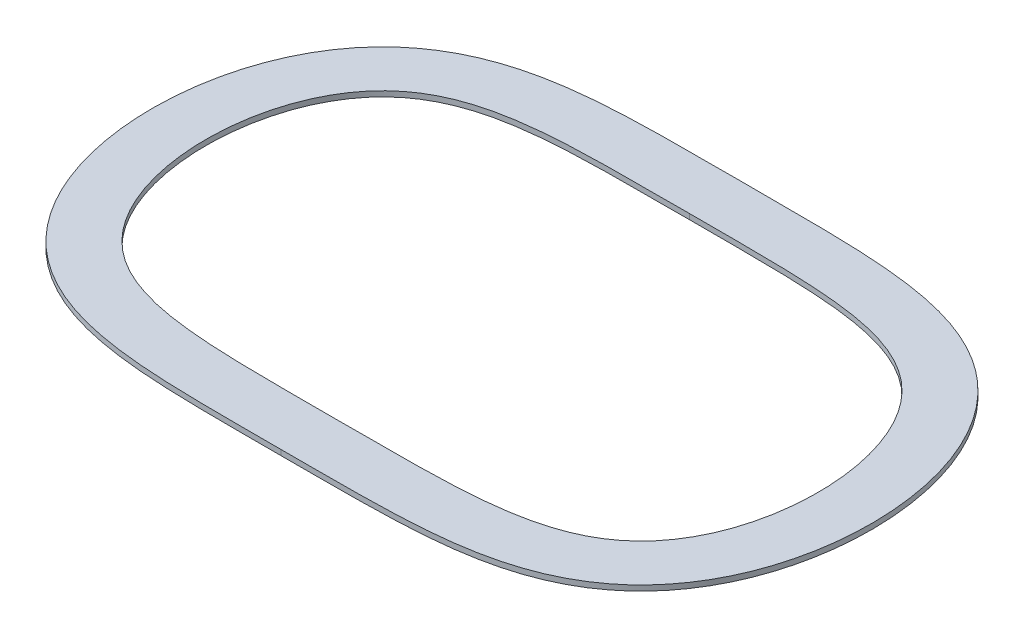
SolidWorks part; units mm, degrees
ref_plane "Front Plane" through (0, 0, 0) normal (0, 0, 1) x (1, 0, 0)
ref_plane "Top Plane" through (0, 0, 0) normal (0, 1, 0) x (1, 0, 0)
ref_plane "Right Plane" through (0, 0, 0) normal (1, 0, 0) x (0, 0, -1)
sketch "Sketch1" plane through (0, 0, 0) normal (0, 1, 0) x (1, 0, 0)
  spline S0 degree 4 poles (0, 129.0994) (4.3298, 129.0999) (12.9895, 129.0995) (25.9763, 129.0992) (43.2902, 129.014) (60.6007, 128.6712) (77.8947, 127.8129) (95.543, 126.046) (113.014, 122.896) (130.0464, 117.7971) (146.1581, 110.2269) (160.4313, 100.265) (172.6933, 87.9119) (182.6634, 73.6634) (190.3404, 58.0791) (195.8654, 41.6227) (199.4008, 24.6362) (201.0699, 7.3707) (200.9352, -9.9735) (198.9912, -27.2107) (195.1663, -44.1354) (189.3287, -60.4854) (181.3147, -75.9018) (170.9944, -89.9023) (157.8662, -102.4377) (141.9679, -112.6829) (124.642, -119.7567) (106.7084, -124.2192) (88.4462, -126.9034) (70.0513, -128.3227) (45.6298, -129.0998) (25.3491, -129.0993) (10.1399, -129.0994) (0, -129.0994) knots 0 0 0 0 0 0.03122 0.06244 0.093642 0.124843 0.156053 0.187263 0.221451 0.252662 0.283872 0.315082 0.346292 0.377502 0.408713 0.439923 0.471133 0.502344 0.533554 0.564765 0.595975 0.627185 0.658396 0.689606 0.720816 0.757371 0.793926 0.823852 0.853778 0.890332 0.926886 1 1 1 1 1 construction
  spline S1 degree 4 poles (0, 129.0994) (4.3298, 129.0999) (12.9895, 129.0995) (25.9763, 129.0992) (43.2902, 129.014) (60.6007, 128.6712) (77.8947, 127.8129) (95.543, 126.046) (113.014, 122.896) (130.0464, 117.7971) (146.1581, 110.2269) (160.4313, 100.265) (172.6933, 87.9119) (182.6634, 73.6634) (190.3404, 58.0791) (195.8654, 41.6227) (199.4008, 24.6362) (201.0699, 7.3707) (200.9352, -9.9735) (198.9912, -27.2107) (195.1663, -44.1354) (189.3287, -60.4854) (181.3147, -75.9018) (170.9944, -89.9023) (157.8662, -102.4377) (141.9679, -112.6829) (124.642, -119.7567) (106.7084, -124.2192) (88.4462, -126.9034) (70.0513, -128.3227) (45.6298, -129.0998) (25.3491, -129.0993) (10.1399, -129.0994) (0, -129.0994) knots 0 0 0 0 0 0.03122 0.06244 0.093642 0.124843 0.156053 0.187263 0.221451 0.252662 0.283872 0.315082 0.346292 0.377502 0.408713 0.439923 0.471133 0.502344 0.533554 0.564765 0.595975 0.627185 0.658396 0.689606 0.720816 0.757371 0.793926 0.823852 0.853778 0.890332 0.926886 1 1 1 1 1
  spline S2 degree 4 poles (0, 129.0994) (-4.3298, 129.0999) (-12.9895, 129.0995) (-25.9763, 129.0992) (-43.2902, 129.014) (-60.6007, 128.6712) (-77.8947, 127.8129) (-95.543, 126.046) (-113.014, 122.896) (-130.0464, 117.7971) (-146.1581, 110.2269) (-160.4313, 100.265) (-172.6933, 87.9119) (-182.6634, 73.6634) (-190.3404, 58.0791) (-195.8654, 41.6227) (-199.4008, 24.6362) (-201.07, 7.3707) (-200.9352, -9.9735) (-198.9912, -27.2107) (-195.1663, -44.1354) (-189.3287, -60.4854) (-181.3147, -75.9018) (-170.9944, -89.9023) (-157.8662, -102.4377) (-141.9679, -112.6829) (-124.642, -119.7567) (-106.7084, -124.2192) (-88.4462, -126.9034) (-70.0513, -128.3227) (-45.6298, -129.0998) (-25.3491, -129.0993) (-10.1399, -129.0994) (0, -129.0994) knots 0 0 0 0 0 0.03122 0.06244 0.093642 0.124843 0.156053 0.187263 0.221451 0.252662 0.283872 0.315082 0.346292 0.377502 0.408713 0.439923 0.471133 0.502344 0.533554 0.564765 0.595975 0.627185 0.658396 0.689606 0.720816 0.757371 0.793926 0.823852 0.853778 0.890332 0.926886 1 1 1 1 1 construction
  spline S3 degree 4 poles (0, 129.0994) (-4.3298, 129.0999) (-12.9895, 129.0995) (-25.9763, 129.0992) (-43.2902, 129.014) (-60.6007, 128.6712) (-77.8947, 127.8129) (-95.543, 126.046) (-113.014, 122.896) (-130.0464, 117.7971) (-146.1581, 110.2269) (-160.4313, 100.265) (-172.6933, 87.9119) (-182.6634, 73.6634) (-190.3404, 58.0791) (-195.8654, 41.6227) (-199.4008, 24.6362) (-201.07, 7.3707) (-200.9352, -9.9735) (-198.9912, -27.2107) (-195.1663, -44.1354) (-189.3287, -60.4854) (-181.3147, -75.9018) (-170.9944, -89.9023) (-157.8662, -102.4377) (-141.9679, -112.6829) (-124.642, -119.7567) (-106.7084, -124.2192) (-88.4462, -126.9034) (-70.0513, -128.3227) (-45.6298, -129.0998) (-25.3491, -129.0993) (-10.1399, -129.0994) (0, -129.0994) knots 0 0 0 0 0 0.03122 0.06244 0.093642 0.124843 0.156053 0.187263 0.221451 0.252662 0.283872 0.315082 0.346292 0.377502 0.408713 0.439923 0.471133 0.502344 0.533554 0.564765 0.595975 0.627185 0.658396 0.689606 0.720816 0.757371 0.793926 0.823852 0.853778 0.890332 0.926886 1 1 1 1 1
extrude "body" add sketch "Sketch1" along normal blind 3 contours S1 S3
sketch "Sketch6" plane through (0, 3, 0) normal (0, 1, 0) x (1, 0, 0)
  spline S5 degree 3 poles (-1285.0609, -2635.3961) (-864.743, -75.7384) (-425.088, -99.3062) (19.1852, -99.0955) (23.9815, -99.0904) (33.5738, -99.0537) (38.3699, -99.0221) (47.9616, -98.8962) (52.7579, -98.802) (62.3467, -98.4962) (67.1336, -98.285) (76.6828, -97.6696) (81.4451, -97.2657) (90.9316, -96.1585) (95.6558, -95.456) (102.6989, -94.0635) (105.0393, -93.5425) (108.5366, -92.6558) (109.7001, -92.3427) (112.0221, -91.6775) (113.1817, -91.3249) (118.9246, -89.468) (123.3747, -87.6745) (129.7643, -84.3748) (131.8465, -83.1733) (134.8899, -81.2003) (135.894, -80.5119) (137.8536, -79.0903) (138.8101, -78.3567) (143.4771, -74.5763) (146.8407, -71.1906) (150.6186, -66.542) (151.3528, -65.5915) (152.7797, -63.6497) (153.4733, -62.657) (155.4863, -59.6292) (156.7253, -57.5647) (160.1696, -51.2497) (162.1054, -46.8788) (164.5604, -40.1222) (165.3033, -37.8364) (166.3108, -34.36) (166.6291, -33.1922) (167.2268, -30.8567) (167.507, -29.6871) (168.8178, -23.8304) (169.5816, -19.117) (170.5999, -9.6403) (170.8539, -4.8769) (170.8586, 2.3051) (170.7971, 4.7053) (170.6075, 8.3151) (170.528, 9.5208) (170.3371, 11.9209) (170.2256, 13.117) (169.5883, 19.0778) (168.8243, 23.784) (166.7551, 33.0633) (165.4507, 37.6366) (163.0193, 44.3799) (162.1291, 46.6081) (160.6593, 49.9173) (160.1456, 51.0173) (159.078, 53.1894) (158.524, 54.2618) (155.6502, 59.5536) (153.0206, 63.5638) (149.2401, 68.2433) (148.4591, 69.1624) (146.8451, 70.9655) (146.0094, 71.852) (143.4475, 74.429) (141.6634, 76.0417) (136.0871, 80.5693) (132.0698, 83.1727) (126.7078, 85.9558) (125.6156, 86.4903) (123.4176, 87.5057) (122.3112, 87.9872) (118.9711, 89.3599) (116.7168, 90.1793) (109.885, 92.3962) (105.2389, 93.5553) (98.1742, 94.9611) (95.8032, 95.3737) (91.0346, 96.1061) (88.6465, 96.4244) (81.481, 97.263) (76.6986, 97.6685) (67.1268, 98.2855) (62.3375, 98.4965) (52.7547, 98.802) (47.9612, 98.8963) (38.372, 99.0221) (33.5762, 99.0536) (23.9839, 99.0903) (19.1872, 99.0954) (-464.0952, 99.336) (-943.5394, 72.5987) (-1333.0254, 2577.4402) knots -2.832138 -2.832138 -2.832138 -2.832138 0.03125 0.03125 0.0625 0.0625 0.09375 0.09375 0.125 0.125 0.15625 0.15625 0.1875 0.1875 0.21875 0.21875 0.234375 0.234375 0.242188 0.242188 0.25 0.25 0.28125 0.28125 0.296875 0.296875 0.304688 0.304688 0.3125 0.3125 0.34375 0.34375 0.351563 0.351563 0.359375 0.359375 0.375 0.375 0.40625 0.40625 0.421875 0.421875 0.429688 0.429688 0.4375 0.4375 0.46875 0.46875 0.5 0.5 0.515625 0.515625 0.523438 0.523438 0.53125 0.53125 0.5625 0.5625 0.59375 0.59375 0.609375 0.609375 0.617188 0.617188 0.625 0.625 0.65625 0.65625 0.664063 0.664063 0.671875 0.671875 0.6875 0.6875 0.71875 0.71875 0.726563 0.726563 0.734375 0.734375 0.75 0.75 0.78125 0.78125 0.796875 0.796875 0.8125 0.8125 0.84375 0.84375 0.875 0.875 0.90625 0.90625 0.9375 0.9375 0.96875 0.96875 4.085999 4.085999 4.085999 4.085999 only from (0, -99.0994) to (0, 99.0994)
  spline S6 degree 3 poles (1397.3598, 2549.0539) (939.196, 72.8031) (462.3033, 99.3351) (-19.1856, 99.0954) (-23.9819, 99.0903) (-33.5745, 99.0536) (-38.3706, 99.0221) (-47.9625, 98.8962) (-52.7589, 98.802) (-62.3478, 98.4961) (-67.1348, 98.285) (-76.6842, 97.6695) (-81.4467, 97.2655) (-90.9333, 96.1583) (-95.6577, 95.4559) (-102.701, 94.0631) (-105.0415, 93.5419) (-108.5389, 92.655) (-109.7024, 92.3419) (-112.0245, 91.6767) (-113.184, 91.3242) (-118.9268, 89.4676) (-123.3764, 87.6734) (-129.7661, 84.374) (-131.8484, 83.1724) (-134.8917, 81.1991) (-135.8958, 80.5106) (-137.8552, 79.089) (-138.8116, 78.3554) (-143.4783, 74.5751) (-146.8418, 71.1894) (-150.6197, 66.5406) (-151.354, 65.59) (-152.7809, 63.6482) (-153.4746, 62.6552) (-155.4873, 59.6275) (-156.7262, 57.5631) (-160.1704, 51.2481) (-162.1061, 46.8771) (-164.561, 40.1203) (-165.3039, 37.8343) (-166.3115, 34.3577) (-166.6296, 33.19) (-167.2273, 30.8546) (-167.5074, 29.685) (-168.8181, 23.8284) (-169.5818, 19.1151) (-170.6, 9.6383) (-170.854, 4.8748) (-170.8586, -2.3075) (-170.797, -4.7078) (-170.6074, -8.3179) (-170.5278, -9.5236) (-170.3369, -11.9235) (-170.2254, -13.1195) (-169.588, -19.0801) (-168.8239, -23.7862) (-166.7545, -33.0656) (-165.4499, -37.6391) (-163.0181, -44.3828) (-162.1279, -46.6111) (-160.6577, -49.9206) (-160.1439, -51.0207) (-159.0763, -53.1926) (-158.5224, -54.2649) (-155.6487, -59.5563) (-153.0188, -63.5663) (-149.2378, -68.246) (-148.4568, -69.1651) (-146.8426, -70.9683) (-146.0067, -71.8547) (-143.4449, -74.4313) (-141.661, -76.0438) (-136.0848, -80.5711) (-132.067, -83.1741) (-126.7046, -85.9575) (-125.6124, -86.4921) (-123.4146, -87.5073) (-122.3081, -87.9887) (-118.9681, -89.3609) (-116.7139, -90.18) (-109.8822, -92.3972) (-105.2359, -93.5559) (-98.1709, -94.9615) (-95.7998, -95.3742) (-91.0309, -96.1066) (-88.6431, -96.4249) (-81.478, -97.2633) (-76.6958, -97.6687) (-67.1244, -98.2856) (-62.3352, -98.4966) (-52.7528, -98.8021) (-47.9595, -98.8963) (-38.3706, -99.0221) (-33.5751, -99.0537) (-23.983, -99.0904) (-19.1865, -99.0955) (426.659, -99.307) (868.5614, -75.5661) (1217.4028, -2663.1697) knots -3.074556 -3.074556 -3.074556 -3.074556 0.03125 0.03125 0.0625 0.0625 0.09375 0.09375 0.125 0.125 0.15625 0.15625 0.1875 0.1875 0.21875 0.21875 0.234375 0.234375 0.242187 0.242187 0.25 0.25 0.28125 0.28125 0.296875 0.296875 0.304687 0.304687 0.3125 0.3125 0.34375 0.34375 0.351562 0.351562 0.359375 0.359375 0.375 0.375 0.40625 0.40625 0.421875 0.421875 0.429687 0.429687 0.4375 0.4375 0.46875 0.46875 0.5 0.5 0.515625 0.515625 0.523437 0.523437 0.53125 0.53125 0.5625 0.5625 0.59375 0.59375 0.609375 0.609375 0.617187 0.617187 0.625 0.625 0.65625 0.65625 0.664062 0.664062 0.671875 0.671875 0.6875 0.6875 0.71875 0.71875 0.726562 0.726562 0.734375 0.734375 0.75 0.75 0.78125 0.78125 0.796875 0.796875 0.8125 0.8125 0.84375 0.84375 0.875 0.875 0.90625 0.90625 0.9375 0.9375 0.96875 0.96875 3.842203 3.842203 3.842203 3.842203 only from (0, 99.0994) to (0, -99.0994)
  spline S7 degree 3 poles (0, -99.0994) (4.7963, -99.0994) (9.5926, -99.1) (19.1852, -99.0955) (23.9815, -99.0904) (33.5738, -99.0537) (38.3699, -99.0221) (47.9616, -98.8962) (52.7579, -98.802) (62.3467, -98.4962) (67.1336, -98.285) (76.6828, -97.6696) (81.4451, -97.2657) (90.9316, -96.1585) (95.6558, -95.456) (102.6989, -94.0635) (105.0393, -93.5425) (108.5366, -92.6558) (109.7001, -92.3427) (112.0221, -91.6775) (113.1817, -91.3249) (118.9246, -89.468) (123.3747, -87.6745) (129.7643, -84.3748) (131.8465, -83.1733) (134.8899, -81.2003) (135.894, -80.5119) (137.8536, -79.0903) (138.8101, -78.3567) (143.4771, -74.5763) (146.8407, -71.1906) (150.6186, -66.542) (151.3528, -65.5915) (152.7797, -63.6497) (153.4733, -62.657) (155.4863, -59.6292) (156.7253, -57.5647) (160.1696, -51.2497) (162.1054, -46.8788) (164.5604, -40.1222) (165.3033, -37.8364) (166.3108, -34.36) (166.6291, -33.1922) (167.2268, -30.8567) (167.507, -29.6871) (168.8178, -23.8304) (169.5816, -19.117) (170.5999, -9.6403) (170.8539, -4.8769) (170.8586, 2.3051) (170.7971, 4.7053) (170.6075, 8.3151) (170.528, 9.5208) (170.3371, 11.9209) (170.2256, 13.117) (169.5883, 19.0778) (168.8243, 23.784) (166.7551, 33.0633) (165.4507, 37.6366) (163.0193, 44.3799) (162.1291, 46.6081) (160.6593, 49.9173) (160.1456, 51.0173) (159.078, 53.1894) (158.524, 54.2618) (155.6502, 59.5536) (153.0206, 63.5638) (149.2401, 68.2433) (148.4591, 69.1624) (146.8451, 70.9655) (146.0094, 71.852) (143.4475, 74.429) (141.6634, 76.0417) (136.0871, 80.5693) (132.0698, 83.1727) (126.7078, 85.9558) (125.6156, 86.4903) (123.4176, 87.5057) (122.3112, 87.9872) (118.9711, 89.3599) (116.7168, 90.1793) (109.885, 92.3962) (105.2389, 93.5553) (98.1742, 94.9611) (95.8032, 95.3737) (91.0346, 96.1061) (88.6465, 96.4244) (81.481, 97.263) (76.6986, 97.6685) (67.1268, 98.2855) (62.3375, 98.4965) (52.7547, 98.802) (47.9612, 98.8963) (38.372, 99.0221) (33.5762, 99.0536) (23.9839, 99.0903) (19.1872, 99.0954) (9.5937, 99.1002) (4.7969, 99.0999) (0, 99.0994) knots 0 0 0 0 0.03125 0.03125 0.0625 0.0625 0.09375 0.09375 0.125 0.125 0.15625 0.15625 0.1875 0.1875 0.21875 0.21875 0.234375 0.234375 0.242188 0.242188 0.25 0.25 0.28125 0.28125 0.296875 0.296875 0.304688 0.304688 0.3125 0.3125 0.34375 0.34375 0.351563 0.351563 0.359375 0.359375 0.375 0.375 0.40625 0.40625 0.421875 0.421875 0.429688 0.429688 0.4375 0.4375 0.46875 0.46875 0.5 0.5 0.515625 0.515625 0.523438 0.523438 0.53125 0.53125 0.5625 0.5625 0.59375 0.59375 0.609375 0.609375 0.617188 0.617188 0.625 0.625 0.65625 0.65625 0.664063 0.664063 0.671875 0.671875 0.6875 0.6875 0.71875 0.71875 0.726563 0.726563 0.734375 0.734375 0.75 0.75 0.78125 0.78125 0.796875 0.796875 0.8125 0.8125 0.84375 0.84375 0.875 0.875 0.90625 0.90625 0.9375 0.9375 0.96875 0.96875 1 1 1 1
  spline S8 degree 3 poles (0, 99.0994) (-4.7964, 99.0999) (-9.5928, 99.1002) (-19.1856, 99.0954) (-23.9819, 99.0903) (-33.5745, 99.0536) (-38.3706, 99.0221) (-47.9625, 98.8962) (-52.7589, 98.802) (-62.3478, 98.4961) (-67.1348, 98.285) (-76.6842, 97.6695) (-81.4467, 97.2655) (-90.9333, 96.1583) (-95.6577, 95.4559) (-102.701, 94.0631) (-105.0415, 93.5419) (-108.5389, 92.655) (-109.7024, 92.3419) (-112.0245, 91.6767) (-113.184, 91.3242) (-118.9268, 89.4676) (-123.3764, 87.6734) (-129.7661, 84.374) (-131.8484, 83.1724) (-134.8917, 81.1991) (-135.8958, 80.5106) (-137.8552, 79.089) (-138.8116, 78.3554) (-143.4783, 74.5751) (-146.8418, 71.1894) (-150.6197, 66.5406) (-151.354, 65.59) (-152.7809, 63.6482) (-153.4746, 62.6552) (-155.4873, 59.6275) (-156.7262, 57.5631) (-160.1704, 51.2481) (-162.1061, 46.8771) (-164.561, 40.1203) (-165.3039, 37.8343) (-166.3115, 34.3577) (-166.6296, 33.19) (-167.2273, 30.8546) (-167.5074, 29.685) (-168.8181, 23.8284) (-169.5818, 19.1151) (-170.6, 9.6383) (-170.854, 4.8748) (-170.8586, -2.3075) (-170.797, -4.7078) (-170.6074, -8.3179) (-170.5278, -9.5236) (-170.3369, -11.9235) (-170.2254, -13.1195) (-169.588, -19.0801) (-168.8239, -23.7862) (-166.7545, -33.0656) (-165.4499, -37.6391) (-163.0181, -44.3828) (-162.1279, -46.6111) (-160.6577, -49.9206) (-160.1439, -51.0207) (-159.0763, -53.1926) (-158.5224, -54.2649) (-155.6487, -59.5563) (-153.0188, -63.5663) (-149.2378, -68.246) (-148.4568, -69.1651) (-146.8426, -70.9683) (-146.0067, -71.8547) (-143.4449, -74.4313) (-141.661, -76.0438) (-136.0848, -80.5711) (-132.067, -83.1741) (-126.7046, -85.9575) (-125.6124, -86.4921) (-123.4146, -87.5073) (-122.3081, -87.9887) (-118.9681, -89.3609) (-116.7139, -90.18) (-109.8822, -92.3972) (-105.2359, -93.5559) (-98.1709, -94.9615) (-95.7998, -95.3742) (-91.0309, -96.1066) (-88.6431, -96.4249) (-81.478, -97.2633) (-76.6958, -97.6687) (-67.1244, -98.2856) (-62.3352, -98.4966) (-52.7528, -98.8021) (-47.9595, -98.8963) (-38.3706, -99.0221) (-33.5751, -99.0537) (-23.983, -99.0904) (-19.1865, -99.0955) (-9.5934, -99.1) (-4.7967, -99.0994) (0, -99.0994) knots 0 0 0 0 0.03125 0.03125 0.0625 0.0625 0.09375 0.09375 0.125 0.125 0.15625 0.15625 0.1875 0.1875 0.21875 0.21875 0.234375 0.234375 0.242187 0.242187 0.25 0.25 0.28125 0.28125 0.296875 0.296875 0.304687 0.304687 0.3125 0.3125 0.34375 0.34375 0.351562 0.351562 0.359375 0.359375 0.375 0.375 0.40625 0.40625 0.421875 0.421875 0.429687 0.429687 0.4375 0.4375 0.46875 0.46875 0.5 0.5 0.515625 0.515625 0.523437 0.523437 0.53125 0.53125 0.5625 0.5625 0.59375 0.59375 0.609375 0.609375 0.617187 0.617187 0.625 0.625 0.65625 0.65625 0.664062 0.664062 0.671875 0.671875 0.6875 0.6875 0.71875 0.71875 0.726562 0.726562 0.734375 0.734375 0.75 0.75 0.78125 0.78125 0.796875 0.796875 0.8125 0.8125 0.84375 0.84375 0.875 0.875 0.90625 0.90625 0.9375 0.9375 0.96875 0.96875 1 1 1 1
  dimension "D1" = 30
extrude "cut-inside" cut sketch "Sketch6" against normal blind 50
